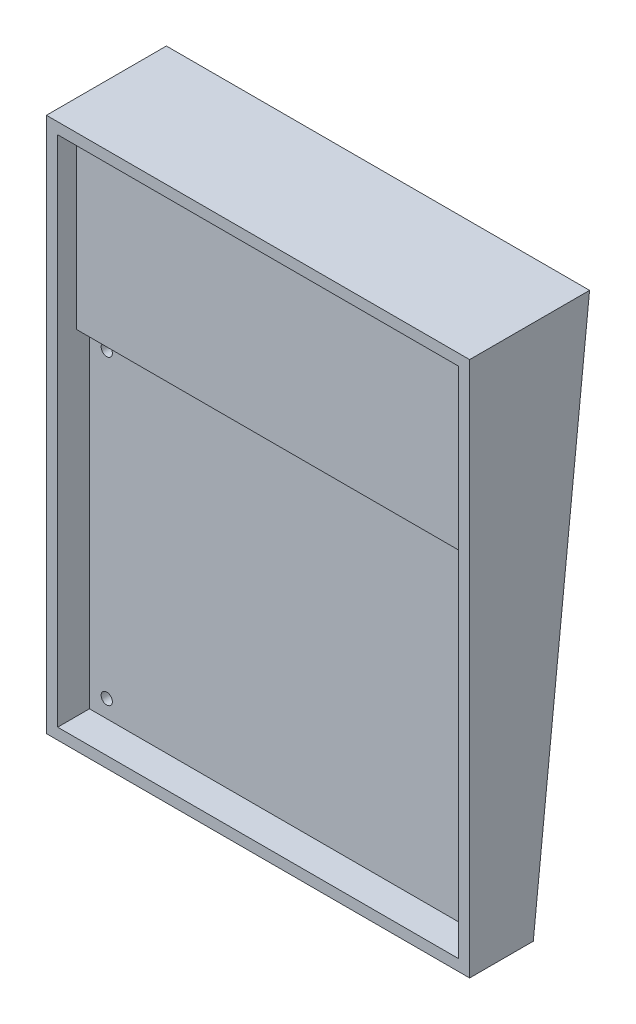
SolidWorks part; units mm, degrees
ref_plane "前基準面" through (0, 0, 0) normal (0, 0, 1) x (1, 0, 0)
ref_plane "上基準面" through (0, 0, 0) normal (0, 1, 0) x (1, 0, 0)
ref_plane "右基準面" through (0, 0, 0) normal (1, 0, 0) x (0, 0, -1)
sketch "草圖1" plane through (0, 0, 0) normal (0, 0, 1) x (1, 0, 0)
  line L1 (0, 0) -> (105, 0)
  line L2 (0, 0) -> (0, 135)
  line L3 (0, 135) -> (105, 135)
  line L4 (105, 0) -> (105, 135)
  circle A0 centre (3.61, 3.68) radius 1.5
  circle A1 centre (101.26, 3.68) radius 1.5
  circle A2 centre (3.61, 84.24) radius 1.5
  circle A3 centre (101.26, 84.24) radius 1.5
  dimension "D3" = 3
  dimension "D6" = 3
  dimension "D9" = 3
  dimension "D12" = 3
  dimension "D1" = 135
  dimension "D2" = 105
  dimension "D4" = 3.68
  dimension "D5" = 3.61
  dimension "D7" = 3.68
  dimension "D8" = 3.74
  dimension "D10" = 80.56
  dimension "D11" = 3.61
  dimension "D13" = 3.74
  dimension "D14" = 80.56
extrude "填料-伸長1" add sketch "草圖1" along normal blind 1
sketch "草圖3" plane through (0, 0, 1) normal (0, 0, 1) x (1, 0, 0)
  line L0 (105, 135) -> (0, 135) construction
  line L1 (-1, 136) -> (106, 136)
  line L2 (-1, 136) -> (-1, -1)
  line L3 (-1, -1) -> (106, -1)
  line L4 (106, 136) -> (106, -1)
  line L5 (105, 0) -> (105, 135) construction
  line L6 (0, 0) -> (105, 0) construction
  line L7 (0, 135) -> (0, 0) construction
  line L9 (-4, 139) -> (109, 139)
  line L10 (-4, 139) -> (-4, -4)
  line L11 (-4, -4) -> (109, -4)
  line L12 (109, 139) -> (109, -4)
  dimension "D1" = 1
  dimension "D2" = 1
  dimension "D3" = 1
  dimension "D4" = 1
  dimension "D5" = 3
  dimension "D6" = 3
  dimension "D7" = 3
  dimension "D8" = 3
extrude "填料-伸長2" add sketch "草圖3" along normal blind 8.5 separate body
extrude "填料-伸長3" add sketch "草圖3<3>" against normal blind 8.5 contours L9 L12 L11 L10
sketch "草圖3<3>" plane through (0, 0, 1) normal (0, 0, 1) x (1, 0, 0) same geometry as "草圖3"
extrude "除料-伸長1" cut sketch "草圖1<2>" along normal blind 6 and the other way blind 5 contours A2 | A3 | A0 | A1
sketch "草圖1<2>" plane through (0, 0, 0) normal (0, 0, 1) x (1, 0, 0) same geometry as "草圖1"
sketch "草圖4" plane through (0, 0, 1) normal (0, 0, 1) x (1, 0, 0)
  line L0 (106, -1) -> (106, 136) construction
  line L1 (-1, 136) -> (106, 136)
  line L2 (-1, 136) -> (-1, 88.49)
  line L3 (-1, 88.49) -> (106, 88.49)
  line L4 (106, 136) -> (106, 88.49)
  circle A0 centre (101.26, 84.24) radius 1.5 construction
  dimension "D1" = 4.25
extrude "填料-伸長4" add sketch "草圖4" along normal blind 3.5
sketch "草圖5" plane through (-4, 0, 0) normal (-1, 0, 0) x (0, 0, 1)
  line L0 (-7.5, 139) -> (-22.5299, 139)
  line L1 (-22.5299, 139) -> (-7.5, -4)
  line L2 (-7.5, -4) -> (-7.5, 139)
  dimension "D1" = 84
extrude "填料-伸長5" add sketch "草圖5" against normal up to surface (113 mm away) up to face at (109, 67.5, 1)
